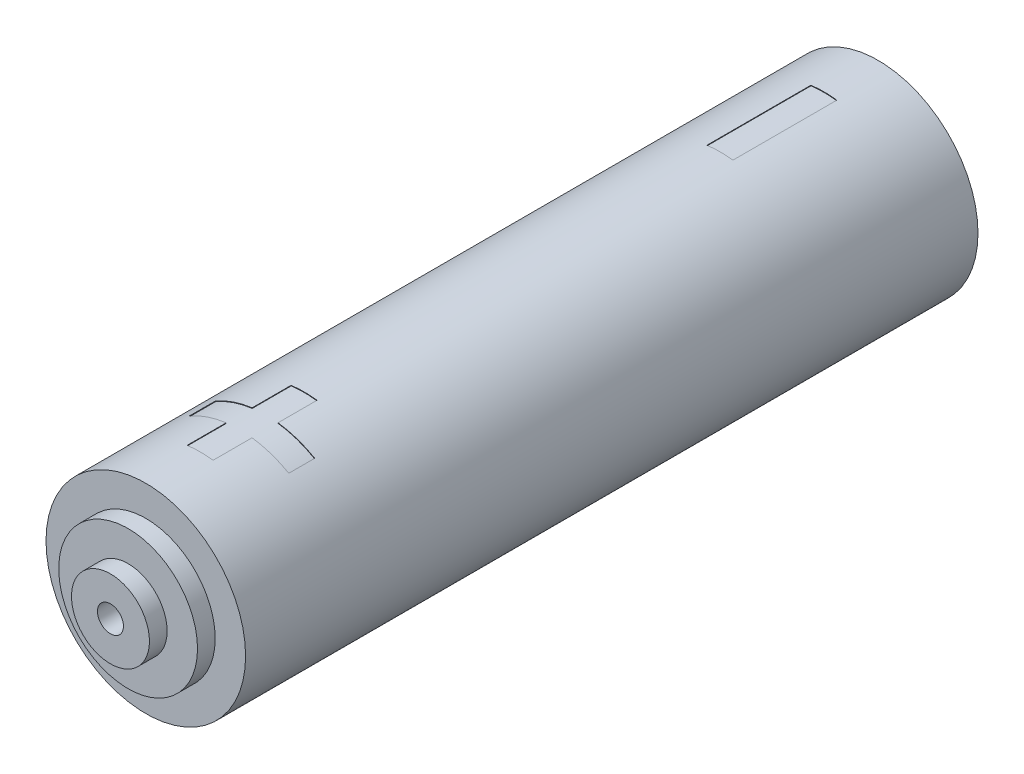
SolidWorks part; units mm, degrees
material "Handl."
ref_plane "Płaszczyzna przednia" through (0, 0, 0) normal (0, 0, 1) x (1, 0, 0)
ref_plane "Płaszczyzna górna" through (0, 0, 0) normal (0, 1, 0) x (1, 0, 0)
ref_plane "Płaszczyzna prawa" through (0, 0, 0) normal (1, 0, 0) x (0, 0, -1)
sketch "Szkic1" plane through (0, 0, 0) normal (1, 0, 0) x (0, 0, -1)
  line L0 (-77.25, 0) -> (77.25, 0) construction
  line L1 (-77.25, 0) -> (-77.25, 7.5)
  line L2 (-77.25, 7.5) -> (-73.85, 7.5)
  line L3 (-73.85, 7.5) -> (-73.85, 13.35)
  line L4 (-73.85, 13.35) -> (-70.45, 13.35)
  line L5 (-70.45, 13.35) -> (-70.45, 19.2)
  line L6 (-70.45, 19.2) -> (70.45, 19.2)
  line L7 (70.45, 19.2) -> (70.45, 7.5)
  line L8 (70.45, 7.5) -> (77.25, 7.5)
  line L9 (77.25, 7.5) -> (77.25, 0)
  line L10 (-77.25, 0) -> (77.25, 0)
  point P3 (0, 19.2)
  dimension "D1" = 154.5
  dimension "D2" = 15
  dimension "D3" = 15
  dimension "D4" = 140.9
  dimension "D5" = 38.4
revolve "Obrót1" add sketch "Szkic1" angle 360 about L0
hole_wizard "Otwór gwintowany M61" positions "Szkic2" profile "Szkic3" tap size "M6" standard "DIN"
sketch "Szkic2" plane through (0, 0, 77.25) normal (0, 0, 1) x (1, 0, 0)
  point P0 (0, 0)
sketch "Szkic3" plane through (0, 0, 77.25) normal (1, 0, 0) x (0, -1, 0)
  line L0 (0, 0) -> (0, 8.5022)
  line L1 (0, 8.5022) -> (2.5, 7)
  line L2 (2.5, 7) -> (2.5, 0)
  line L5 (2.5, 0) -> (0, 0)
  line L10 (0, 8.5022) -> (-2.5, 7) construction
  line L11 (0, -6.35) -> (0, 107.95) construction
  dimension "Średnica wiertła gwintu" = 5
  dimension "Głębokość otworu gwintowanego" = 7
  dimension "Kąt wiertła" = 118
cosmetic thread "Gwint otworu1" parameters "D1"=2, "D2"=6
hole_wizard "Otwór gwintowany M62" positions "Szkic4" profile "Szkic5" tap size "M6" standard "DIN"
sketch "Szkic4" plane through (0, 0, -77.25) normal (0, 0, -1) x (-1, 0, 0)
  point P0 (0, 0)
sketch "Szkic5" plane through (0, 0, -77.25) normal (1, 0, 0) x (0, 1, 0)
  line L0 (0, 0) -> (0, 8.5022)
  line L1 (0, 8.5022) -> (2.5, 7)
  line L2 (2.5, 7) -> (2.5, 0)
  line L5 (2.5, 0) -> (0, 0)
  line L10 (0, 8.5022) -> (-2.5, 7) construction
  line L11 (0, -6.35) -> (0, 107.95) construction
  dimension "Średnica wiertła gwintu" = 5
  dimension "Głębokość otworu gwintowanego" = 7
  dimension "Kąt wiertła" = 118
cosmetic thread "Gwint otworu2" parameters "D1"=2, "D2"=6
ref_plane "Płaszczyzna1" through (0, 50, 0) normal (0, 1, 0) x (1, 0, 0)
sketch "Szkic6" plane through (0, 50, 0) normal (0, 1, 0) x (1, 0, 0)
  line L0 (0, 0) -> (0, -50) construction
  line L1 (-2.5, -47.5) -> (-2.5, -40)
  line L2 (-10, -52.5) -> (-2.5, -52.5)
  line L3 (-10, -52.5) -> (-10, -47.5)
  line L4 (-10, -47.5) -> (-2.5, -47.5)
  line L5 (10, -52.5) -> (10, -47.5)
  line L6 (-10, -52.5) -> (10, -47.5) construction
  line L7 (-10, -47.5) -> (10, -52.5) construction
  line L8 (-2.5, -60) -> (2.5, -60)
  line L9 (-2.5, -60) -> (-2.5, -52.5)
  line L10 (-2.5, -40) -> (2.5, -40)
  line L11 (2.5, -60) -> (2.5, -52.5)
  line L12 (-2.5, -60) -> (2.5, -40) construction
  line L13 (-2.5, -40) -> (2.5, -60) construction
  line L14 (0, 0) -> (0, 50) construction
  line L15 (2.5, -47.5) -> (10, -47.5)
  line L16 (2.5, -47.5) -> (2.5, -40)
  line L18 (2.5, -52.5) -> (10, -52.5)
  line L19 (2.5, 40) -> (-2.5, 40)
  line L20 (2.5, 40) -> (2.5, 60)
  line L21 (2.5, 60) -> (-2.5, 60)
  line L22 (-2.5, 40) -> (-2.5, 60)
  line L23 (2.5, 40) -> (-2.5, 60) construction
  line L24 (2.5, 60) -> (-2.5, 40) construction
  dimension "D1" = 50
  dimension "D2" = 5
  dimension "D3" = 20
  dimension "D4" = 5
  dimension "D5" = 20
wrap "Zawijaj1" sketch "Szkic6" wrap type deboss source sketch "Szkic6" thickness 0.1 face at (19.2, 0, 70.45) parameters "D1"=0.1
